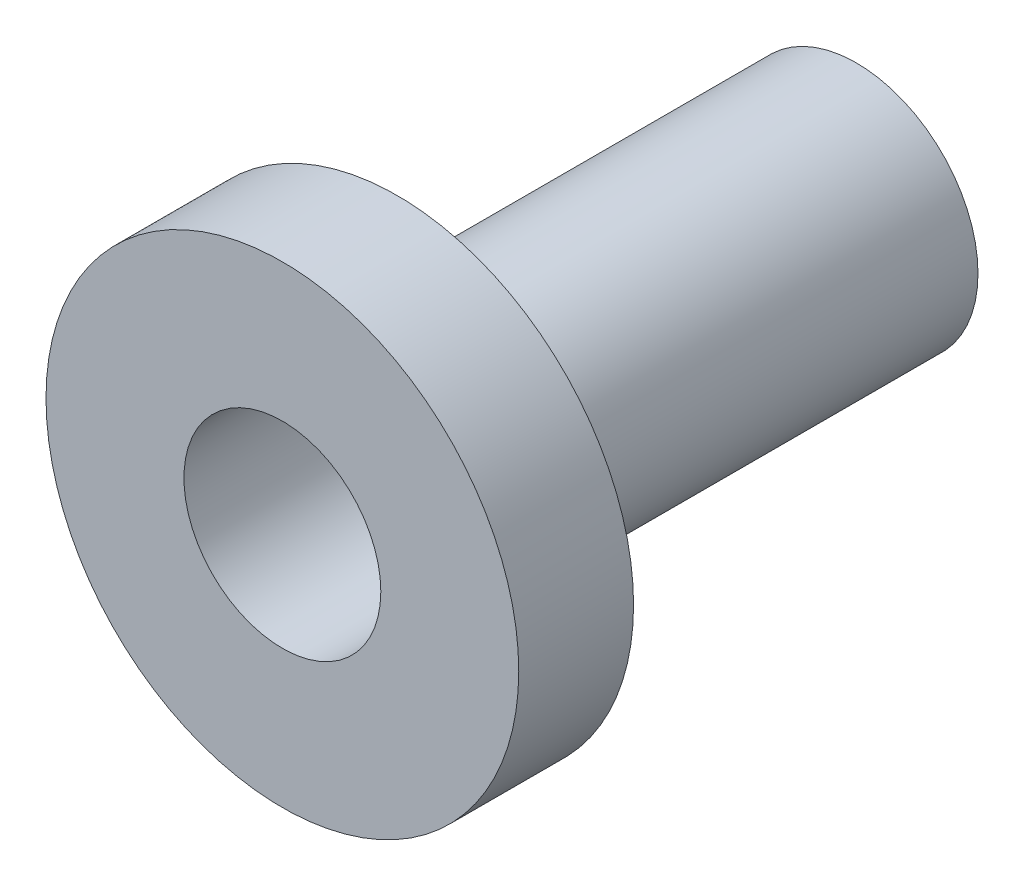
SolidWorks part; units mm, degrees
material "ABS"
ref_plane "Front Plane" through (0, 0, 0) normal (0, 0, 1) x (1, 0, 0)
ref_plane "Top Plane" through (0, 0, 0) normal (0, 1, 0) x (1, 0, 0)
ref_plane "Right Plane" through (0, 0, 0) normal (1, 0, 0) x (0, 0, -1)
sketch "Sketch1" plane through (0, 0, 0) normal (0, 0, 1) x (1, 0, 0)
  circle A0 centre (0, 0) radius 18
extrude "Boss-Extrude1" add sketch "Sketch1" along normal blind 85
sketch "Sketch2" plane through (0, 0, 85) normal (0, 0, 1) x (1, 0, 0)
  circle A0 centre (0, 0) radius 14.576
extrude "Cut-Extrude1" cut sketch "Sketch2" against normal blind 60
sketch "Sketch3" plane through (0, 0, 0) normal (0, 0, -1) x (-1, 0, 0)
  circle A0 centre (0, 0) radius 4.3644
extrude "Cut-Extrude2" cut sketch "Sketch3" against normal blind 60
sketch "Sketch4" plane through (0, 0, 85) normal (0, 0, 1) x (1, 0, 0)
  circle A0 centre (0, 0) radius 14.576
  circle A1 centre (0, 0) radius 35
extrude "Boss-Extrude2" add sketch "Sketch4" against normal blind 17
sketch "Sketch5" plane through (0, 0, 85) normal (0, 0, 1) x (1, 0, 0)
  circle A0 centre (1.619, -28.1194) radius 3.1814
extrude "Cut-Extrude3" cut sketch "Sketch5" against normal blind 4 from offset 13 offset against normal yes
